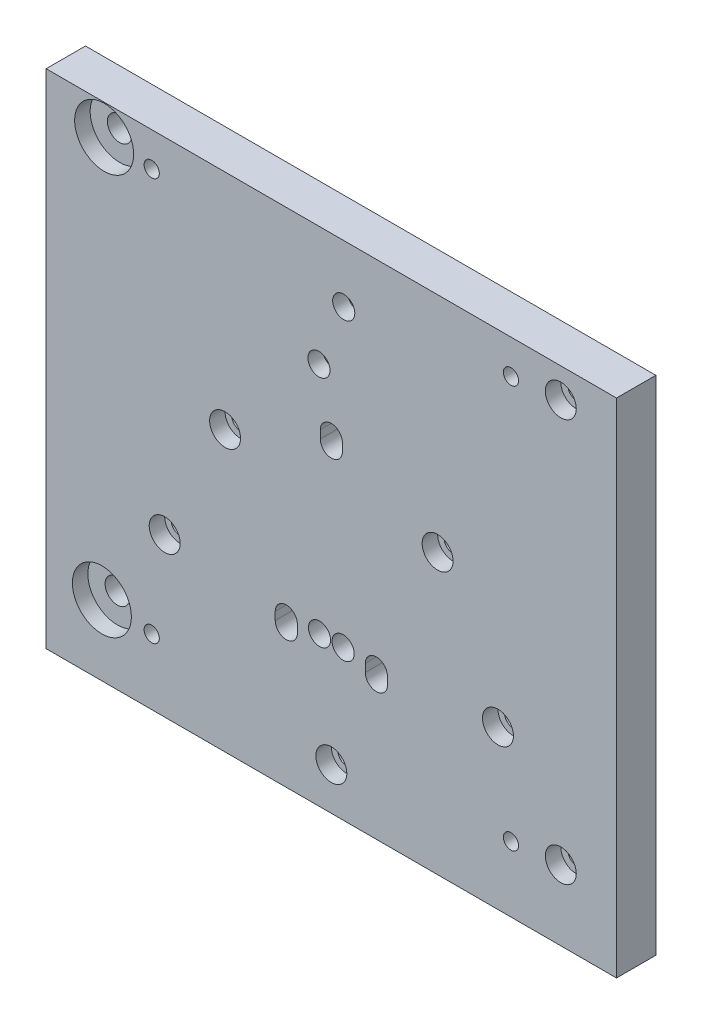
SolidWorks part; units mm, degrees
material "Beech"
ref_plane "Front Plane" through (0, 0, 0) normal (0, 0, 1) x (1, 0, 0)
ref_plane "Top Plane" through (0, 0, 0) normal (0, 1, 0) x (1, 0, 0)
ref_plane "Right Plane" through (0, 0, 0) normal (1, 0, 0) x (0, 0, -1)
sketch "Sketch1" plane through (0, 0, 0) normal (0, 0, 1) x (1, 0, 0)
  line L1 (2.065, -202.025) -> (-182.085, -202.025)
  line L2 (2.065, -202.025) -> (2.065, -55.975)
  line L3 (2.065, -55.975) -> (-182.085, -55.975)
  line L4 (-182.085, -202.025) -> (-182.085, -55.975)
  line L5 (2.065, -202.025) -> (-182.085, -55.975) construction
  line L6 (2.065, -55.975) -> (-182.085, -202.025) construction
  point P0 (-90.01, -129)
  dimension "D1" = 184.15
  dimension "D2" = 146.05
extrude "Boss-Extrude1" add sketch "Sketch1" along normal blind 12.7
ref_plane "CL" through (0, -129, 0) normal (0, -1, 0) x (-1, 0, 0)
sketch "Sketch5" plane through (0, -202.025, 0) normal (0, -1, 0) x (1, 0, 0)
  line L4 (-182.085, 0) -> (2.065, 0)
  line L5 (2.065, 0) -> (2.065, 12.7)
  line L6 (2.065, 12.7) -> (-182.085, 12.7)
  line L7 (-182.085, 12.7) -> (-182.085, 0)
  line L8 (-182.085, 0) -> (2.065, 0)
  line L9 (2.065, 0) -> (2.065, 12.7)
  line L10 (2.065, 12.7) -> (-182.085, 12.7)
  line L11 (-182.085, 12.7) -> (-182.085, 0)
  dimension "D1" = 0
extrude "Boss-Extrude2" add sketch "Sketch5" along normal up to surface (16.125 mm away)
hole_wizard "CBORE for M5 SHCS2" positions "Sketch2" profile "Sketch3" counterbore size "M5" standard "ANSI Metric" end condition up to next
sketch "Sketch2" plane through (0, 0, 12.7) normal (0, 0, 1) x (1, 0, 0)
  point P0 (-55.7, -127.9887)
  point P2 (-124.32, -127.9887)
  point P17 (-90.01, -204.5313)
  point P19 (-143.8109, -167.1)
  point P21 (-36.2091, -167.1)
sketch "Sketch3" plane through (-55.7, -127.9887, 12.7) normal (1, 0, 0) x (0, -1, 0)
  line L0 (0, 0) -> (0, 12.7)
  line L1 (0, 12.7) -> (2.9, 12.7)
  line L3 (2.9, 12.7) -> (2.9, 5)
  line L4 (2.9, 5) -> (5, 5)
  line L5 (5, 5) -> (5, 0)
  line L7 (5, 0) -> (0, 0)
  line L11 (0, -6.35) -> (0, 107.95) construction
  dimension "Thru Hole Dia." = 5.8
  dimension "Thru Hole Depth" = 12.7
  dimension "C'Bore Dia." = 10
  dimension "C'Bore Depth" = 5
hole_wizard "CBORE for M5 SHCS3" positions "Sketch6" profile "Sketch7" counterbore size "M5" standard "ANSI Metric" end condition through all
sketch "Sketch6" plane through (0, 0, 12.7) normal (0, 0, 1) x (1, 0, 0)
  point P0 (-15.925, -65.5)
  point P2 (-15.925, -195.4887)
  point P4 (-164.095, -195.4887)
  point P6 (-163.361, -65.7922)
  point P7 (0, 0)
  point P8 (-163.361, -65.7922)
  point P9 (-164.095, -195.4887)
  point P10 (0, 0)
sketch "Sketch7" plane through (-15.925, -65.5, 12.7) normal (1, 0, 0) x (0, -1, 0)
  line L0 (0, 0) -> (0, 12.7)
  line L1 (0, 12.7) -> (2.65, 12.7)
  line L3 (2.65, 12.7) -> (2.65, 5)
  line L4 (2.65, 5) -> (5, 5)
  line L5 (5, 5) -> (5, 0)
  line L7 (5, 0) -> (0, 0)
  line L11 (0, -6.35) -> (0, 107.95) construction
  dimension "Thru Hole Dia." = 5.3
  dimension "Thru Hole Depth" = 12.7
  dimension "C'Bore Dia." = 10
  dimension "C'Bore Depth" = 5
sketch "Sketch12" plane through (0, 0, 0) normal (0, 0, -1) x (-1, 0, 0)
  circle A0 centre (164.095, -65.5) radius 5
  circle A1 centre (164.095, -196.2787) radius 5
  dimension "D1" = 10
hole_wizard "CBORE SLOT for #6 Socket Head Cap Screw1" positions "Sketch15" profile "Sketch16" size "#6" standard "ANSI Inch" slot yes end condition through all
sketch "Sketch15" plane through (0, 0, 12.7) normal (0, 0, 1) x (1, 0, 0)
  line L0 (-90.01, -117.15) -> (-90.01, -110.8) construction
  line L1 (-90.01, -218.15) -> (-90.01, -55.975) construction
  line L2 (-182.085, -218.15) -> (2.065, -218.15) construction
  line L3 (2.065, -55.975) -> (-182.085, -55.975) construction
  point P0 (-90.01, -113.975)
  point P6 (-104.5514, -171.9951)
  point P17 (-75.4686, -171.9951)
  dimension "D1" = 6.35
sketch "Sketch16" plane through (-90.01, -113.975, 12.7) normal (1, 0, 0) x (0, -1, 0)
  line L0 (0, 0) -> (0, 12.7)
  line L1 (0, 12.7) -> (1.8986, 12.7)
  line L3 (1.8986, 12.7) -> (1.8986, 7.3152)
  line L4 (1.8986, 7.3152) -> (3.5725, 7.3152)
  line L5 (3.5725, 7.3152) -> (3.5725, 0)
  line L7 (3.5725, 0) -> (0, 0)
  line L11 (0, -6.35) -> (0, 107.95) construction
  dimension "Thru Hole Dia." = 3.7973
  dimension "Thru Hole Depth" = 12.7
  dimension "C'Bore Dia." = 7.145
  dimension "C'Bore Depth" = 7.3152
hole_wizard "CBORE for #6 Socket Head Cap Screw1" positions "Sketch19" profile "Sketch18" counterbore size "#6" standard "ANSI Inch" end condition through all
sketch "Sketch19" plane through (0, 0, 12.7) normal (0, 0, 1) x (1, 0, 0)
  line L0 (-90.01, -218.15) -> (-90.01, -55.975) construction
  line L1 (-182.085, -218.15) -> (2.065, -218.15) construction
  line L2 (2.065, -55.975) -> (-182.085, -55.975) construction
  point P0 (-93.82, -169.8501)
  point P15 (-86.2, -169.8501)
  dimension "D1" = 48.2999
  dimension "D2" = 3.81
sketch "Sketch18" plane through (-93.82, -169.8501, 12.7) normal (1, 0, 0) x (0, -1, 0)
  line L0 (0, 0) -> (0, 12.7)
  line L1 (0, 12.7) -> (2.1526, 12.7)
  line L3 (2.1526, 12.7) -> (2.1526, 7.3152)
  line L4 (2.1526, 7.3152) -> (3.5725, 7.3152)
  line L5 (3.5725, 7.3152) -> (3.5725, 0)
  line L7 (3.5725, 0) -> (0, 0)
  line L11 (0, -6.35) -> (0, 107.95) construction
  dimension "Thru Hole Dia." = 4.3053
  dimension "Thru Hole Depth" = 12.7
  dimension "C'Bore Dia." = 7.145
  dimension "C'Bore Depth" = 7.3152
hole_wizard "#8 Clearance Hole1" positions "Sketch20" profile "Sketch21" hole size "#8" standard "ANSI Inch" end condition through all
sketch "Sketch20" plane through (0, 0, 12.7) normal (0, 0, 1) x (1, 0, 0)
  point P0 (-32.01, -66.9887)
  point P4 (-148.01, -66.9887)
  point P6 (-148.01, -196.9887)
  point P8 (-32.01, -196.9887)
sketch "Sketch21" plane through (-32.01, -66.9887, 12.7) normal (1, 0, 0) x (0, -1, 0)
  line L0 (0, 0) -> (0, 12.7)
  line L1 (0, 12.7) -> (2.4574, 12.7)
  line L2 (2.4574, 12.7) -> (2.4574, 0)
  line L5 (2.4574, 0) -> (0, 0)
  line L11 (0, -6.35) -> (0, 107.95) construction
  dimension "Thru Hole Dia." = 4.9149
  dimension "Thru Hole Depth" = 12.7
hole_wizard "CBORE for #6 Socket Head Cap Screw2" positions "Sketch22" profile "Sketch23" counterbore size "#6" standard "ANSI Inch" end condition through all
sketch "Sketch22" plane through (0, 0, 12.7) normal (0, 0, 1) x (1, 0, 0)
  point P0 (-94.01, -94.5397)
  point P2 (-86.01, -74.5397)
sketch "Sketch23" plane through (-94.01, -94.5397, 12.7) normal (1, 0, 0) x (0, -1, 0)
  line L0 (0, 0) -> (0, 12.7)
  line L1 (0, 12.7) -> (2.1527, 12.7)
  line L3 (2.1527, 12.7) -> (2.1526, 4.7752)
  line L4 (2.1526, 4.7752) -> (3.5725, 4.7752)
  line L5 (3.5725, 4.7752) -> (3.5725, 0)
  line L7 (3.5725, 0) -> (0, 0)
  line L11 (0, -6.35) -> (0, 107.95) construction
  dimension "Thru Hole Dia." = 4.3053
  dimension "Thru Hole Depth" = 12.7
  dimension "C'Bore Dia." = 7.145
  dimension "C'Bore Depth" = 4.7752
sketch "Sketch24" plane through (0, 0, 0) normal (0, 0, -1) x (-1, 0, 0)
  circle A0 centre (148.01, -66.9887) radius 9.525
  circle A1 centre (32.01, -66.9887) radius 9.525
  circle A2 centre (32.01, -196.9887) radius 9.525
  circle A3 centre (148.01, -196.9887) radius 9.525
  dimension "D1" = 19.05
extrude "Cut-Extrude2" cut sketch "Sketch24" against normal blind 3.175
sketch "Sketch25" plane through (0, 0, 12.7) normal (0, 0, 1) x (1, 0, 0)
  circle A0 centre (-163.361, -65.7922) radius 3.9687
  circle A1 centre (-164.095, -195.4887) radius 3.9687
  circle A2 centre (-164.095, -195.4887) radius 5 construction
  dimension "D1" = 7.9375
extrude "Cut-Extrude3" cut sketch "Sketch25" against normal up to next
sketch "Sketch26" plane through (0, 0, 12.7) normal (0, 0, 1) x (1, 0, 0)
  circle A0 centre (-164.095, -195.4887) radius 9.525
  circle A1 centre (-163.361, -65.7922) radius 9.525
  circle A3 centre (-163.361, -65.7922) radius 5 construction
  point P5 (0, 0)
  dimension "D1" = 19.05
extrude "Cut-Extrude4" cut sketch "Sketch26" against normal up to surface (5 mm away) up to face at (-168.0638, -195.4887, 7.7)
